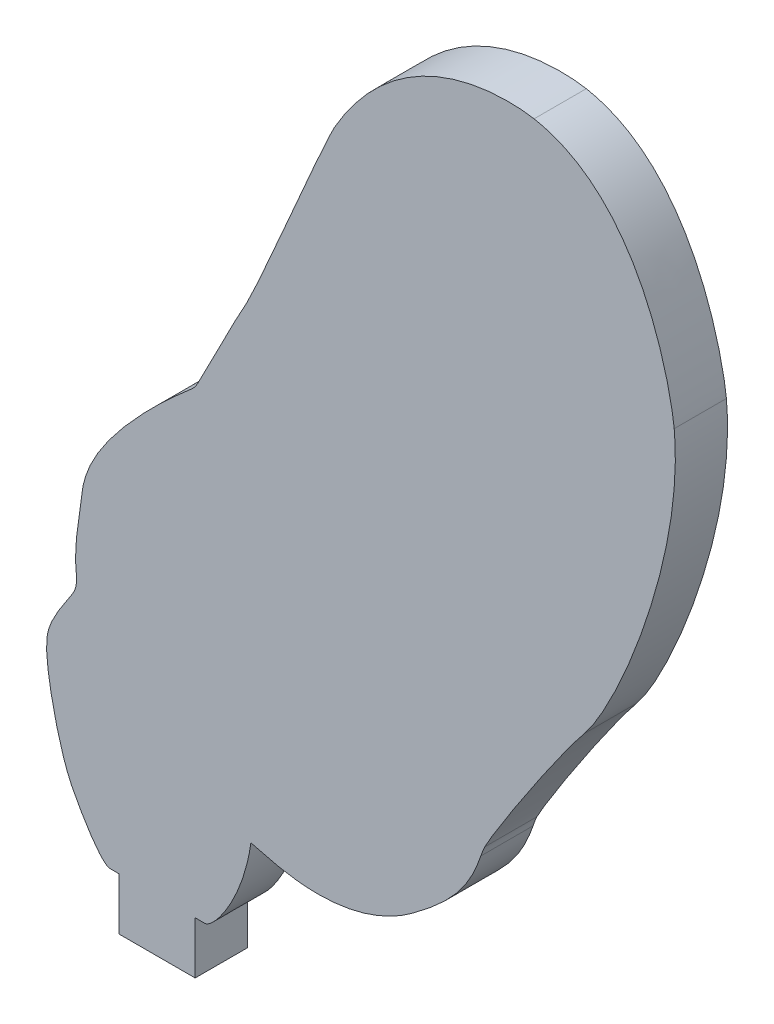
SolidWorks part; units mm, degrees
ref_plane "Front Plane" through (0, 0, 0) normal (0, 0, 1) x (1, 0, 0)
ref_plane "Top Plane" through (0, 0, 0) normal (0, 1, 0) x (1, 0, 0)
ref_plane "Right Plane" through (0, 0, 0) normal (1, 0, 0) x (0, 0, -1)
sketch "Model" plane through (0, 0, 0) normal (0, 0, 1) x (1, 0, 0)
  line L0 (248.2187, -402.2672) -> (248.2103, -402.3276)
  line L1 (248.2103, -402.3276) -> (248.2225, -402.4913)
  line L2 (251.0191, -409.3304) -> (255.1835, -409.3304)
  spline S0 degree 3 poles (275.8761, -380.1041) (275.8418, -379.5647) (274.7996, -372.3139) (269.7009, -371.3656) knots 0 0 0 0 1 1 1 1
  spline S1 degree 3 poles (269.7009, -371.3656) (269.2075, -371.2738) (264.1373, -370.4626) (260.9041, -376.0844) knots 1 1 1 1 2 2 2 2
  spline S2 degree 3 poles (260.9041, -376.0844) (260.4338, -376.9022) (257.5163, -383.8835) (257.0324, -384.7302) knots 2 2 2 2 3 3 3 3
  spline S3 degree 3 poles (257.0324, -384.7302) (256.6272, -385.4395) (256.1755, -386.3345) (255.7387, -387.2001) knots 3 3 3 3 4 4 4 4
  spline S4 degree 3 poles (255.7387, -387.2001) (255.5009, -387.6714) (255.1137, -388.4391) (254.8636, -388.8991) knots 4 4 4 4 5 5 5 5
  spline S5 degree 3 poles (254.8636, -388.8991) (254.7919, -389.0309) (254.6983, -389.1453) (254.5836, -389.2419) knots 5 5 5 5 6 6 6 6
  spline S6 degree 3 poles (254.5836, -389.2419) (254.0607, -389.6825) (253.2513, -390.4175) (252.4874, -391.2131) knots 6 6 6 6 7 7 7 7
  spline S7 degree 3 poles (252.4874, -391.2131) (250.2217, -393.5726) (249.8536, -394.8706) (249.7738, -395.6417) knots 7 7 7 7 8 8 8 8
  spline S8 degree 3 poles (249.7738, -395.6417) (249.7485, -395.8871) (249.7094, -396.1429) (249.668, -396.4137) knots 8 8 8 8 9 9 9 9
  spline S9 degree 3 poles (249.668, -396.4137) (249.5552, -397.1505) (249.4257, -397.9965) (249.5305, -398.8855) knots 9 9 9 9 10 10 10 10
  spline S10 degree 3 poles (249.5305, -398.8855) (249.565, -399.1778) (249.4895, -399.4746) (249.3229, -399.7172) knots 10 10 10 10 11 11 11 11
  spline S11 degree 3 poles (249.3229, -399.7172) (248.3721, -401.1028) (248.2604, -401.5463) (248.2276, -401.9737) knots 11 11 11 11 12 12 12 12
  spline S12 degree 3 poles (248.2276, -401.9737) (248.2233, -402.0292) (248.2184, -402.1159) (248.2187, -402.2672) knots 12 12 12 12 13 13 13 13
  spline S13 degree 3 poles (248.2225, -402.4913) (248.246, -403.3321) (248.709, -405.7632) (249.3194, -407.0109) knots 15 15 15 15 16 16 16 16
  spline S14 degree 3 poles (249.3194, -407.0109) (249.5235, -407.4282) (250.5546, -409.3304) (251.0191, -409.3304) knots 16 16 16 16 17 17 17 17
  spline S15 degree 3 poles (255.1835, -409.3304) (255.5785, -409.3304) (256.9038, -407.6013) (257.217, -405.238) knots 18 18 18 18 19 19 19 19
  spline S16 degree 3 poles (257.217, -405.238) (257.2824, -405.2537) (257.4008, -405.2855) (257.4765, -405.3059) knots 19 19 19 19 20 20 20 20
  spline S17 degree 3 poles (257.4765, -405.3059) (258.0536, -405.461) (259.0189, -405.7206) (260.1772, -405.7206) knots 20 20 20 20 21 21 21 21
  spline S18 degree 3 poles (260.1772, -405.7206) (261.7016, -405.7206) (263.0918, -405.2732) (264.3093, -404.3906) knots 21 21 21 21 22 22 22 22
  spline S19 degree 3 poles (264.3093, -404.3906) (266.4637, -402.8284) (266.9623, -401.7846) (267.353, -400.6771) knots 22 22 22 22 23 23 23 23
  spline S20 degree 3 poles (267.353, -400.6771) (267.4166, -400.4968) (267.4625, -400.3666) (267.5239, -400.2439) knots 23 23 23 23 24 24 24 24
  spline S21 degree 3 poles (267.5239, -400.2439) (267.9374, -399.4172) (270.6386, -395.2764) (271.9266, -393.7087) knots 24 24 24 24 25 25 25 25
  spline S22 degree 3 poles (271.9266, -393.7087) (273.3761, -391.9444) (276.3421, -385.0268) (275.8761, -380.1041) knots 25 25 25 25 26 26 26 26
base flange "Base-Flange1" sketch "Model" thickness 2.3 reverse thickness direction no parameters "D1"=0.7366
sketch "Sketch6" plane through (0, 0, 0) normal (0, 0, 1) x (1, 0, 0)
  line L0 (251.0191, -409.3304) -> (255.1835, -409.3304) construction
  line L1 (251.4115, -409.3304) -> (254.7615, -409.3304)
  line L2 (251.4115, -409.3304) -> (251.4115, -411.6304)
  line L3 (251.4115, -411.6304) -> (254.7615, -411.6304)
  line L4 (254.7615, -409.3304) -> (254.7615, -411.6304)
  dimension "D1" = 2.3
  dimension "D2" = 3.35
base flange "Tab1" sketch "Sketch6" thickness 2.3 reverse thickness direction no parameters "D1"=0.7366
sketch "Bend-Lines1" [suppressed] plane through (0, 0, 0) normal (0, 1, 0) x (1, 0, 0)
sketch "Bounding-Box1" [suppressed] plane through (0, 0, 0) normal (0, 1, 0) x (1, 0, 0)
sheet metal parameters "Sheet-Metal1" thickness 2.3 parameters "D1"=0.7366
flat pattern "Flat-Pattern1" [suppressed]
sketch "Bend-Lines2" plane through (0, 0, 0) normal (0, 1, 0) x (1, 0, 0)
sketch3d "Bounding-Box2" [suppressed]
  line L0 (14.9019, -26.4166, 0) -> (-6.749, 10.2283, 0) construction
  line L1 (30.8507, -16.9936, 0) -> (9.1997, 19.6513, 0) construction
  line L2 (14.9019, -26.4166, 0) -> (30.8507, -16.9936, 0) construction
  line L3 (-6.749, 10.2283, 0) -> (9.1997, 19.6513, 0) construction
sheet metal parameters "Sheet-Metal2" thickness 2.3 parameters "D1"=0.7366
flat pattern "Flat-Pattern2"
sketch "Bend-Lines3" plane through (0, 0, 0) normal (0, 1, 0) x (1, 0, 0)
sketch3d "Bounding-Box3" [suppressed]
  line L0 (-15.7912, -27.9218, 0) -> (6.749, 10.2283, 0) construction
  line L1 (-31.74, -18.4988, 0) -> (-9.1997, 19.6513, 0) construction
  line L2 (-15.7912, -27.9218, 0) -> (-31.74, -18.4988, 0) construction
  line L3 (6.749, 10.2283, 0) -> (-9.1997, 19.6513, 0) construction
